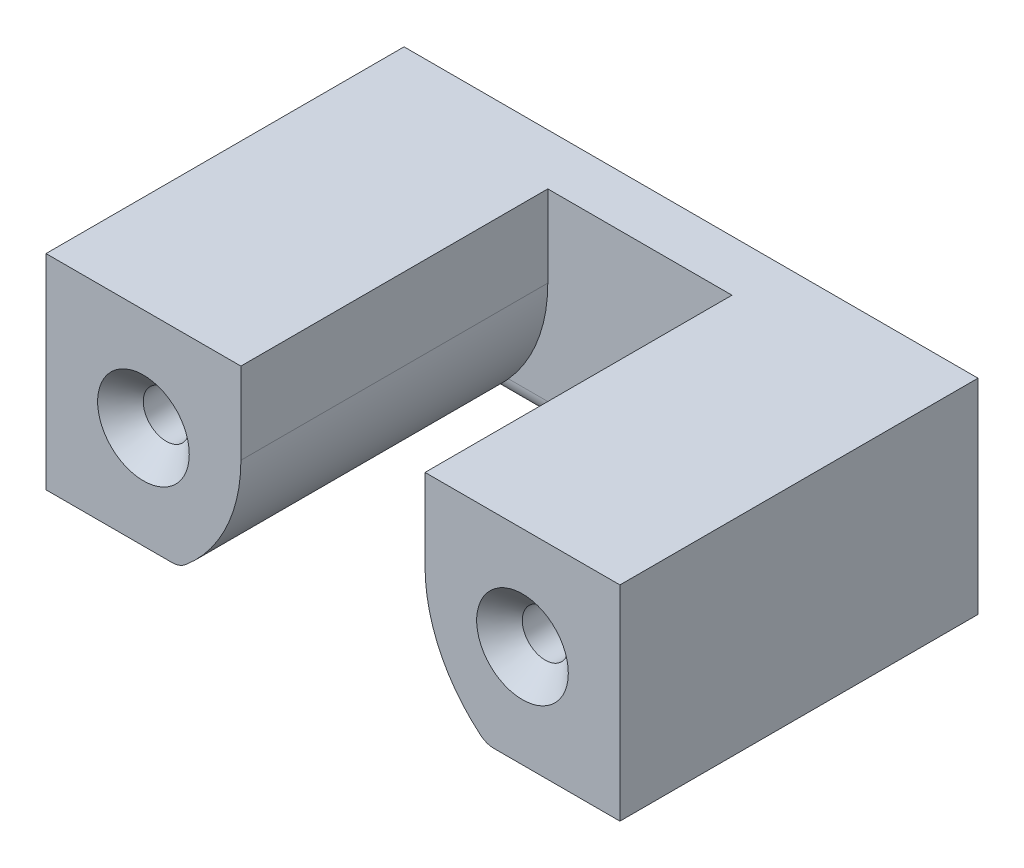
SolidWorks part; units mm, degrees
ref_plane "Спереди" through (0, 0, 0) normal (0, 0, 1) x (1, 0, 0)
ref_plane "Сверху" through (0, 0, 0) normal (0, 1, 0) x (1, 0, 0)
ref_plane "Справа" through (0, 0, 0) normal (1, 0, 0) x (0, 0, -1)
sketch "Эскиз1" plane through (0, 0, 0) normal (0, 0, 1) x (1, 0, 0)
  line L1 (0, 0) -> (56.1, 0)
  line L2 (0, 0) -> (0, 20)
  line L3 (0, 20) -> (56.1, 20)
  line L4 (56.1, 0) -> (56.1, 20)
  dimension "D1" = 56.1
  dimension "D2" = 20
extrude "Бобышка-Вытянуть1" add sketch "Эскиз1" along normal blind 5 contours L1 L4 L3 L2
sketch "Эскиз2" plane through (0, 0, 5) normal (0, 0, 1) x (1, 0, 0)
  line L0 (19.05, 20) -> (19.05, 12.0256)
  line L1 (13.6528, 0.5023) -> (13.05, 0)
  line L2 (28.05, 20) -> (28.05, 0) construction
  line L3 (37.05, 20) -> (37.05, 12.0256)
  line L4 (0, 20) -> (0, 0)
  line L5 (0, 0) -> (56.1, 0)
  line L6 (56.1, 0) -> (56.1, 20)
  line L7 (56.1, 20) -> (0, 20)
  line L8 (0, 20) -> (0, 0)
  line L9 (0, 0) -> (56.1, 0)
  line L10 (56.1, 0) -> (56.1, 20)
  line L11 (56.1, 20) -> (0, 20)
  line L12 (42.4472, 0.5023) -> (43.05, 0)
  line L13 (13.05, 0) -> (43.05, 0)
  line L14 (19.05, 20) -> (37.05, 20)
  arc A0 (13.6528, 0.5023) -> (19.05, 12.0256) centre (4.05, 12.0256) ccw
  arc A1 (42.4472, 0.5023) -> (37.05, 12.0256) centre (52.05, 12.0256) cw
  point P15 (19.05, 5)
  point P18 (37.05, 5)
  line M7 (0, 20) -> (0, 0)
  line M8 (0, 0) -> (56.1, 0)
  line M9 (56.1, 0) -> (56.1, 20)
  line M10 (56.1, 20) -> (0, 20)
  dimension "D5" = 15
  dimension "D2" = 15
  dimension "D3" = 18
  dimension "D4" = 30
  dimension "D1" = 0
extrude "Бобышка-Вытянуть2" add sketch "Эскиз2" along normal blind 30 contours L1 A0 L0 M10 M7 M8 | A1 L12 L9 L3 M9 M10 region at (9.0509, 10.4331, 5) region at (47.0491, 10.4331, 5)
sketch "Эскиз3" plane through (0, 0, 35) normal (0, 0, 1) x (1, 0, 0)
  line L0 (0, 0) -> (13.05, 0) construction
  line L1 (9.525, 20) -> (9.525, 0) construction
  line L2 (19.05, 20) -> (0, 20) construction
  line L3 (46.575, 20) -> (46.575, 0) construction
  line L4 (56.1, 20) -> (37.05, 20) construction
  line L5 (43.05, 0) -> (56.1, 0) construction
  point P0 (9.525, 10)
  point P1 (46.575, 10)
  point P9 (9.525, 10)
hole_wizard "Зенковка для  винта с потайной головкой с внутренним шестигранником M41" positions "Трехмерный эскиз1" profile "Эскиз4" countersink size "M4" standard "Ansi Metric" end condition up to next
sketch3d "Трехмерный эскиз1"
  point P0 (9.525, 10, 35)
  point P3 (46.575, 10, 35)
sketch "Эскиз4" plane through (9.525, 10, 35) normal (1, 0, 0) x (0, -1, 0)
  line L0 (0, 0) -> (0, 35)
  line L1 (0, 35) -> (2.25, 35)
  line L2 (2.25, 35) -> (2.25, 2.23)
  line L3 (2.25, 2.23) -> (4.48, 0)
  line L5 (4.48, 0) -> (0, 0)
  line L6 (-2.25, 2.23) -> (-4.48, 0) construction
  line L11 (0, -6.35) -> (0, 107.95) construction
  dimension "Диаметр сквозного отверстия" = 4.5
  dimension "Глубина сквозного отверстия" = 35
  dimension "Диаметр передней зенковки" = 8.96
  dimension "Угол передней зенковки" = 90
fillet "Скругление1" radius 2 3 edges at (28.05, 0, 5) (43.05, 0, 20) (13.05, 0, 20)
